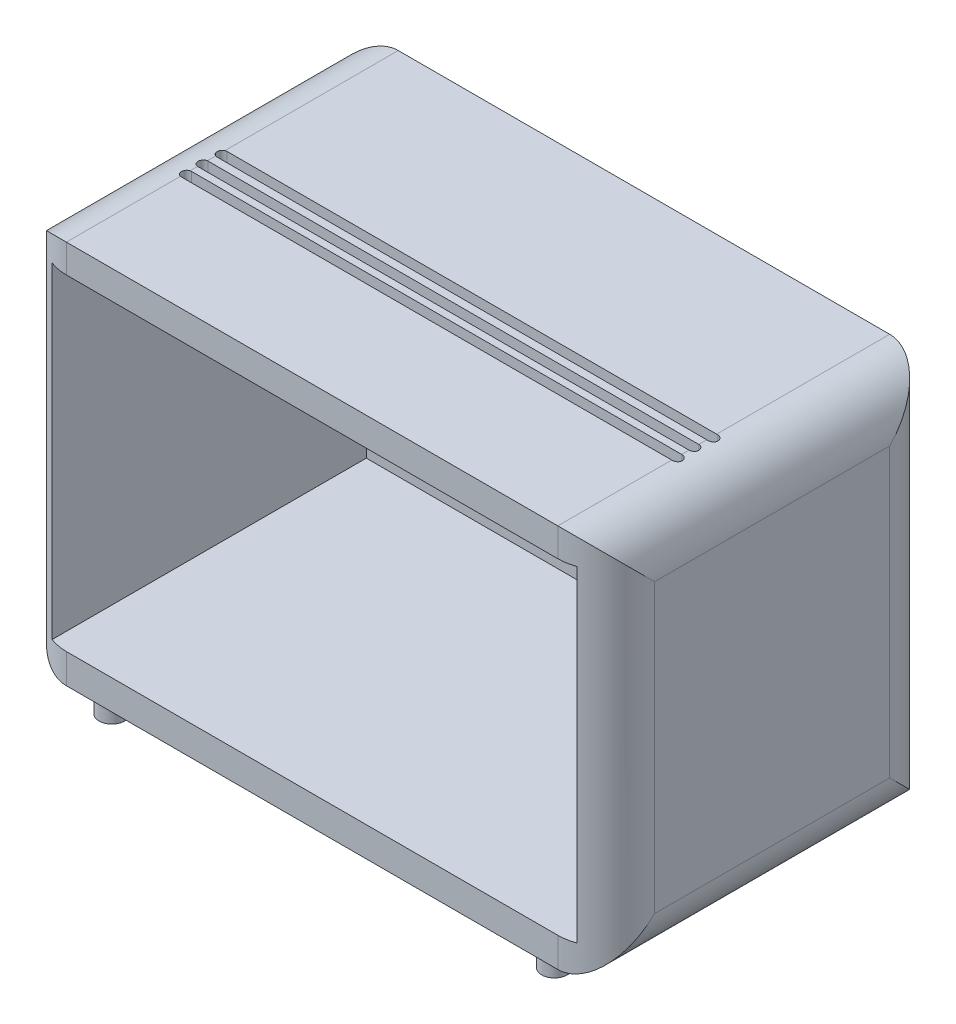
SolidWorks part; units mm, degrees
ref_plane "Ön Düzlem" through (0, 0, 0) normal (0, 0, 1) x (1, 0, 0)
ref_plane "Üst Düzlem" through (0, 0, 0) normal (0, 1, 0) x (1, 0, 0)
ref_plane "Sağ Düzlem" through (0, 0, 0) normal (1, 0, 0) x (0, 0, -1)
sketch "Çizim1" plane through (0, 0, 0) normal (0, 0, 1) x (1, 0, 0)
  line L1 (-50.4208, -30.5103) -> (58.1418, -30.5103)
  line L2 (-50.4208, -30.5103) -> (-50.4208, 36.8819)
  line L3 (-50.4208, 36.8819) -> (58.1418, 36.8819)
  line L4 (58.1418, -30.5103) -> (58.1418, 36.8819)
  line L5 (-56.7925, 42.7634) -> (64.7585, 42.7634)
  line L6 (-56.7925, 42.7634) -> (-56.7925, -36.6368)
  line L7 (-56.7925, -36.6368) -> (64.7585, -36.6368)
  line L8 (64.7585, 42.7634) -> (64.7585, -36.6368)
extrude "Yükseklik-Ekstrüzyon1" add sketch "Çizim1" along normal blind 68.58
sketch "Çizim2" plane through (0, -30.5103, 0) normal (0, 1, 0) x (1, 0, 0)
  line L1 (58.0412, -0.1373) -> (-50.6245, -0.1373)
  line L2 (58.0412, -0.1373) -> (58.0412, -2.9769)
  line L3 (58.0412, -2.9769) -> (-50.6245, -2.9769)
  line L4 (-50.6245, -0.1373) -> (-50.6245, -2.9769)
extrude "Yükseklik-Ekstrüzyon3" add sketch "Çizim2" along normal blind 67.31
sketch "Çizim4" plane through (0, 0, 0.1373) normal (0, 0, -1) x (-1, 0, 0)
  line L1 (-23.9717, 26.1556) -> (19.7974, 26.1556)
  line L2 (-23.9717, 26.1556) -> (-23.9717, -8.6241)
  line L3 (-23.9717, -8.6241) -> (19.7974, -8.6241)
  line L4 (19.7974, 26.1556) -> (19.7974, -8.6241)
extrude "Kes-Ekstrüzyon3" cut sketch "Çizim4" against normal blind 51.308
fillet "Radyus1" radius 10 4 edges at (64.7585, -36.6368, 34.29) (64.7585, 3.0633, 68.58) (64.7585, 42.7634, 34.29) (64.7585, 3.0633, 0)
fillet "Radyus2" radius 10 4 edges at (-56.7925, 42.7634, 34.29) (-56.7925, 3.0633, 68.58) (-56.7925, -36.6368, 34.29) (-56.7925, 3.0633, 0)
sketch "Çizim5" plane through (0, 42.7634, 0) normal (0, 1, 0) x (1, 0, 0)
  line L7 (-46.4232, -36.769) -> (55.0127, -36.769) construction
  line L8 (-46.4232, -35.752) -> (55.0127, -35.752)
  line L9 (-46.4232, -37.786) -> (55.0127, -37.786)
  line L10 (-46.5504, -44.0153) -> (54.8856, -44.0153) construction
  line L11 (-46.5504, -42.9983) -> (54.8856, -42.9983)
  line L12 (-46.5504, -45.0323) -> (54.8856, -45.0323)
  line L13 (-46.6775, -40.4557) -> (54.7585, -40.4557) construction
  line L14 (-46.6775, -39.4387) -> (54.7585, -39.4387)
  line L15 (-46.6775, -41.4727) -> (54.7585, -41.4727)
  arc A4 (-46.4232, -35.752) -> (-46.4232, -37.786) centre (-46.4232, -36.769) ccw
  arc A5 (55.0127, -37.786) -> (55.0127, -35.752) centre (55.0127, -36.769) ccw
  arc A6 (-46.5504, -42.9983) -> (-46.5504, -45.0323) centre (-46.5504, -44.0153) ccw
  arc A7 (54.8856, -45.0323) -> (54.8856, -42.9983) centre (54.8856, -44.0153) ccw
  arc A8 (-46.6775, -39.4387) -> (-46.6775, -41.4727) centre (-46.6775, -40.4557) ccw
  arc A9 (54.7585, -41.4727) -> (54.7585, -39.4387) centre (54.7585, -40.4557) ccw
  point P0 (0, 0)
  point P18 (4.2948, -36.769)
  point P25 (4.1676, -44.0153)
  point P32 (4.0405, -40.4557)
extrude "Kes-Ekstrüzyon6" cut sketch "Çizim5" against normal blind 25.4
sketch "Çizim6" plane through (0, -36.6368, 0) normal (0, -1, 0) x (-1, 0, 0)
  line L0 (-49.5044, -4.227) -> (-49.5044, -64.0147) construction
  line L1 (-46.871, -4.227) -> (-46.871, -64.0147)
  line L2 (-52.1378, -4.227) -> (-52.1378, -64.0147)
  line L3 (41.6686, -4.5254) -> (41.6686, -64.3132) construction
  line L4 (44.302, -4.5254) -> (44.302, -64.3132)
  line L5 (39.0352, -4.5254) -> (39.0352, -64.3132)
  arc A0 (-46.871, -4.227) -> (-52.1378, -4.227) centre (-49.5044, -4.227) ccw
  arc A1 (-52.1378, -64.0147) -> (-46.871, -64.0147) centre (-49.5044, -64.0147) ccw
  arc A2 (44.302, -4.5254) -> (39.0352, -4.5254) centre (41.6686, -4.5254) ccw
  arc A3 (39.0352, -64.3132) -> (44.302, -64.3132) centre (41.6686, -64.3132) ccw
  point P2 (-49.5044, -34.1209)
  point P9 (41.6686, -34.4193)
extrude "Yükseklik-Ekstrüzyon4" add sketch "Çizim6" along normal blind 4.572
